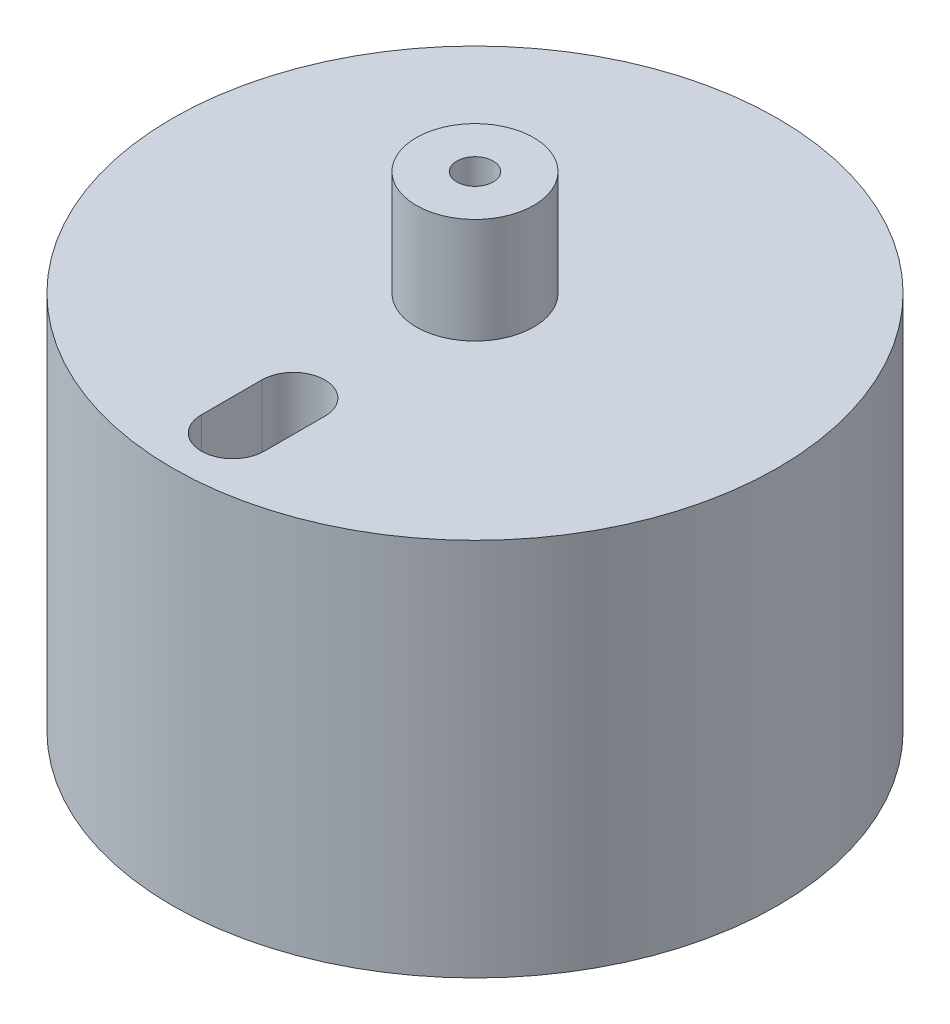
SolidWorks part; units mm, degrees
ref_plane "Front Plane" through (0, 0, 0) normal (0, 0, 1) x (1, 0, 0)
ref_plane "Top Plane" through (0, 0, 0) normal (0, 1, 0) x (1, 0, 0)
ref_plane "Right Plane" through (0, 0, 0) normal (1, 0, 0) x (0, 0, -1)
sketch "Sketch1" plane through (0, 0, 0) normal (0, 1, 0) x (1, 0, 0)
  circle A0 centre (0, 0) radius 25
  dimension "D1" = 50
extrude "Boss-Extrude1" add sketch "Sketch1" along normal blind 40
sketch "Sketch2" plane through (0, 40, 0) normal (0, 1, 0) x (1, 0, 0)
  circle A0 centre (0, 0) radius 25
  circle A1 centre (0, 0) radius 4.85
  dimension "D1" = 50
  dimension "D2" = 9.7
extrude "Cut-Extrude1" cut sketch "Sketch2" against normal blind 8.7
sketch "Sketch3" plane through (0, 31.3, 0) normal (0, 1, 0) x (1, 0, 0)
  line L0 (-2.6, -15) -> (-2.6, -20)
  line L1 (2.6, -15) -> (2.6, -20)
  line L2 (-2.6, -17.5) -> (2.6, -17.5) construction
  arc A0 (2.6, -15) -> (-2.6, -15) centre (0, -15) ccw
  arc A1 (-2.6, -20) -> (2.6, -20) centre (0, -20) ccw
  point P7 (0, -17.5)
  dimension "D1" = 5.2
  dimension "D2" = 5
  dimension "D3" = 15
extrude "Cut-Extrude2" cut sketch "Sketch3" against normal blind 10
sketch "Sketch5" plane through (0, 21.3, 0) normal (0, 1, 0) x (1, 0, 0)
  circle A0 centre (0, -17.5) radius 1.5
  dimension "D1" = 3
extrude "Cut-Extrude3" cut sketch "Sketch5" against normal through all
sketch "Sketch6" plane through (0, 0, 0) normal (0, -1, 0) x (1, 0, 0)
  circle A0 centre (0, 0) radius 1.5
  dimension "D1" = 3
extrude "Cut-Extrude4" cut sketch "Sketch6" against normal through all
